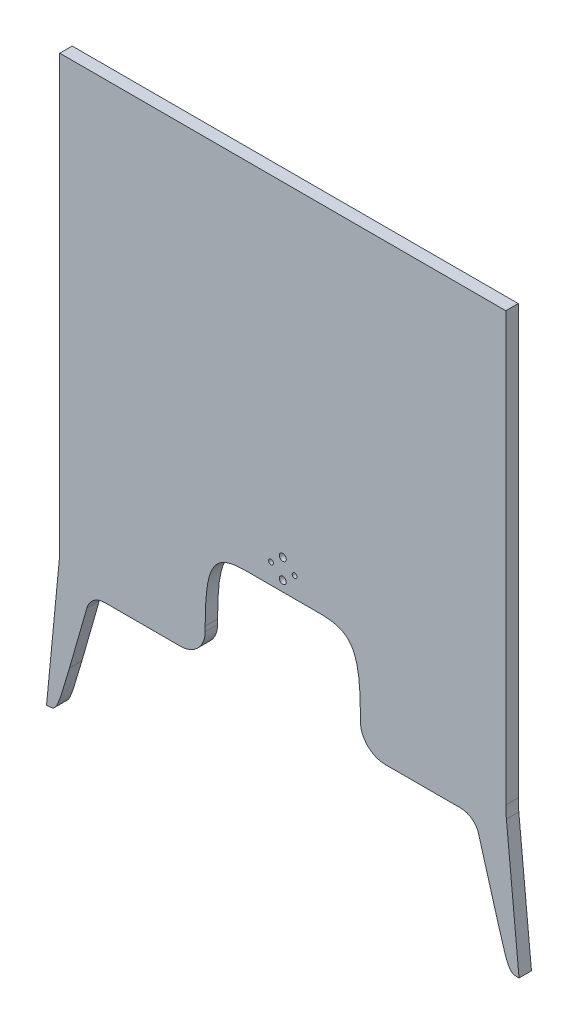
SolidWorks part; units mm, degrees
material "MDF"
ref_plane "Front Plane" through (0, 0, 0) normal (0, 0, 1) x (1, 0, 0)
ref_plane "Top Plane" through (0, 0, 0) normal (0, 1, 0) x (1, 0, 0)
ref_plane "Right Plane" through (0, 0, 0) normal (1, 0, 0) x (0, 0, -1)
sketch "Sketch1" plane through (0, 0, 0) normal (0, 0, 1) x (1, 0, 0)
  line L0 (-228.0888, 0) -> (228.0888, 0)
  line L1 (79.375, -363.22) -> (-79.375, -363.22)
  line L2 (0, -363.22) -> (0, 0) construction
  line L3 (-79.375, -363.22) -> (-79.375, -463.55)
  line L4 (196.3388, -463.55) -> (79.375, -463.55)
  line L5 (-230.9346, -584.2) -> (-196.3388, -463.55)
  line L6 (-230.9346, -584.2) -> (-241.6001, -584.2)
  line L7 (-241.6001, -584.2) -> (-228.0888, -443.879)
  line L8 (-228.0888, -443.879) -> (-228.0888, 0)
  line L9 (-196.3388, -463.55) -> (-79.375, -463.55)
  line L10 (228.0888, -443.879) -> (228.0888, 0)
  line L11 (241.6001, -584.2) -> (228.0888, -443.879)
  line L12 (230.9346, -584.2) -> (241.6001, -584.2)
  line L13 (230.9346, -584.2) -> (196.3388, -463.55)
  line L14 (79.375, -363.22) -> (79.375, -463.55)
  dimension "D1" = 363.22
  dimension "D2" = 158.75
  dimension "D3" = 106
  dimension "D4" = 31.75
  dimension "D5" = 120.65
  dimension "D6" = 174.5
  dimension "D7" = 463.55
  dimension "D8" = 140.97
extrude "Boss-Extrude1" add sketch "Sketch1" along normal blind 12.7
fillet "Fillet2" radius 69.85 1 edges at (-79.375, -363.22, 6.35) second distance 41.275 conic rho 0.6 first distance on face at (-79.375, -413.385, 6.35)
fillet "Fillet3" radius 25.4 1 edges at (-79.375, -463.55, 6.35)
fillet "Fillet4" radius 19.05 1 edges at (-196.3388, -463.55, 6.35)
ref_plane "Plane1" through (-230.9346, -584.2, 0) normal (0, 0, -1) x (-1, 0, 0)
fillet "Fillet5" radius 22.225 1 edges at (-230.9346, -584.2, 6.35) second distance 50.8 conic rho 0.7 first distance on face at (-236.2674, -584.2, 6.35)
fillet "Fillet6" radius 127 1 edges at (-228.0888, -443.879, 6.35)
sketch "Sketch3" plane through (0, 0, 12.7) normal (0, 0, 1) x (1, 0, 0)
  line L0 (0, 0) -> (0, -440.5951) construction
  line L2 (228.0888, 0) -> (-228.0888, 0) construction
  line L4 (0, 0) -> (241.6001, 0)
  line L5 (0, 0) -> (0, -584.2)
  line L6 (0, -584.2) -> (241.6001, -584.2)
  line L7 (241.6001, 0) -> (241.6001, -584.2)
  point P3 (0, 0)
extrude "Cut-Extrude1" cut sketch "Sketch3" against normal up to next
mirror "Mirror5" about plane through (0, 0, -0.3502) normal (-1, 0, 0) of bodies 103
hole_wizard "#8 Clearance Hole1" positions "Sketch4" profile "Sketch5" hole size "#8" standard "ANSI Inch" end condition up to next
sketch "Sketch4" plane through (0, 0, 0) normal (0, 0, -1) x (-1, 0, 0)
  circle A0 centre (12.0772, -342.5825) radius 2.4574 construction
  circle A1 centre (-12.0772, -342.5825) radius 2.4574 construction
  point P0 (12.0772, -342.5825)
  point P2 (-12.0772, -342.5825)
sketch "Sketch5" plane through (-12.0772, -342.5825, 0) normal (1, 0, 0) x (0, 1, 0)
  line L0 (0, 0) -> (0, 12.7)
  line L1 (0, 12.7) -> (2.4574, 12.7)
  line L2 (2.4574, 12.7) -> (2.4574, 0)
  line L5 (2.4574, 0) -> (0, 0)
  line L11 (0, -6.35) -> (0, 107.95) construction
  dimension "Thru Hole Dia." = 4.9149
  dimension "Thru Hole Depth" = 12.7
hole_wizard "1/4 Clearance Hole1" positions "Sketch6" profile "Sketch7" hole size "1/4" standard "ANSI Inch" end condition up to next
sketch "Sketch6" plane through (0, 0, 0) normal (0, 0, -1) x (-1, 0, 0)
  circle A0 centre (0, -352.7425) radius 3.5712 construction
  circle A1 centre (0, -332.4225) radius 3.5712 construction
  point P0 (0, -352.7425)
  point P2 (0, -332.4225)
sketch "Sketch7" plane through (0, -352.7425, 0) normal (1, 0, 0) x (0, 1, 0)
  line L0 (0, 0) -> (0, 12.7)
  line L1 (0, 12.7) -> (3.5712, 12.7)
  line L2 (3.5712, 12.7) -> (3.5712, 0)
  line L5 (3.5712, 0) -> (0, 0)
  line L11 (0, -6.35) -> (0, 107.95) construction
  dimension "Thru Hole Dia." = 7.1425
  dimension "Thru Hole Depth" = 12.7
